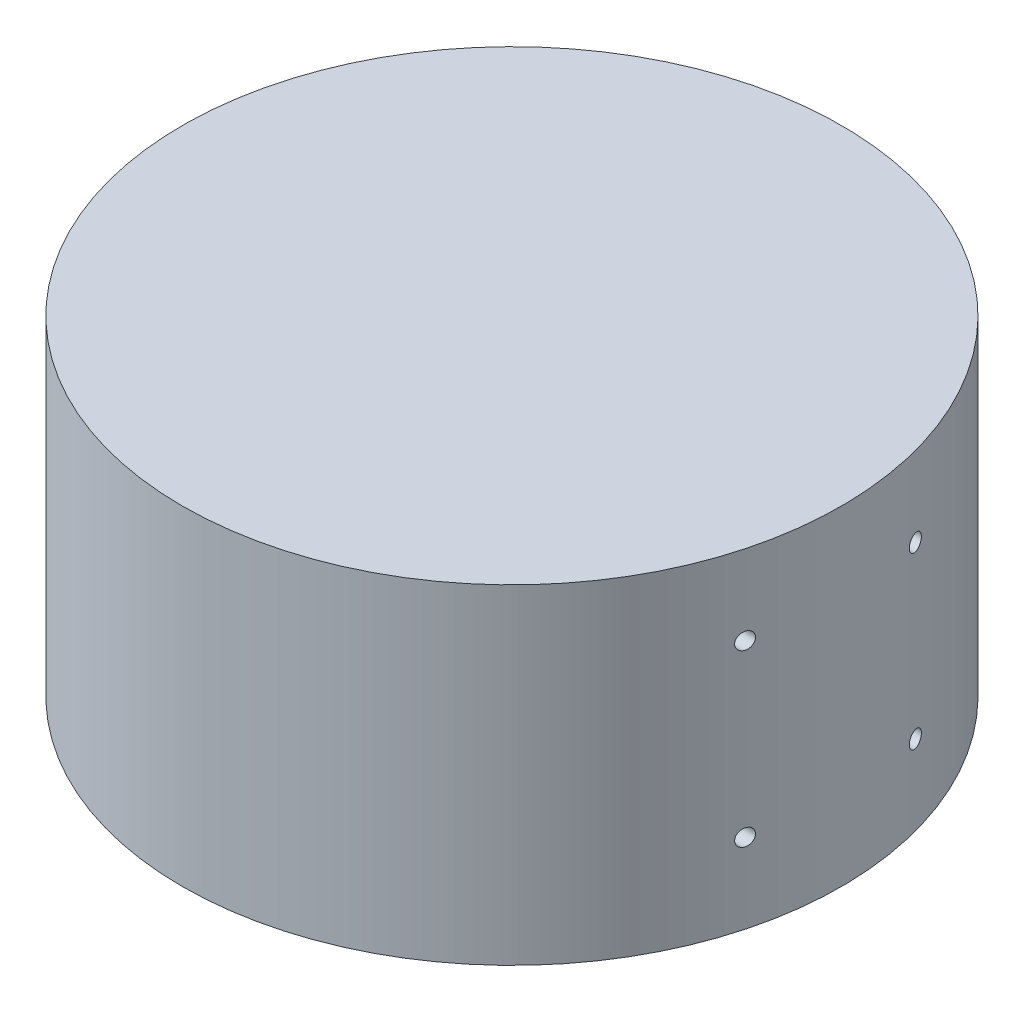
SolidWorks part; units mm, degrees
ref_plane "前视基准面" through (0, 0, 0) normal (0, 0, 1) x (1, 0, 0)
ref_plane "上视基准面" through (0, 0, 0) normal (0, 1, 0) x (1, 0, 0)
ref_plane "右视基准面" through (0, 0, 0) normal (1, 0, 0) x (0, 0, -1)
other "Configuration Table"
sketch "Sketch1" plane through (0, 0, 0) normal (0, 1, 0) x (1, 0, 0)
  circle A0 centre (0, 0) radius 60
extrude "Boss-Extrude1" add sketch "Sketch1" along normal blind 60
sketch "Sketch2" plane through (0, 0, 0) normal (0, 1, 0) x (1, 0, 0)
  circle A0 centre (0, 0) radius 10
extrude "Cut-Extrude1" cut sketch "Sketch2" along normal blind 20
sketch "Sketch3" plane through (0, 0, 0) normal (1, 0, 0) x (0, 0, -1)
  circle A0 centre (-15.5, 45.5) radius 1.5
  circle A1 centre (-15.5, 14.5) radius 1.5
  circle A2 centre (15.5, 14.5) radius 1.5
  circle A3 centre (15.5, 45.5) radius 1.5
extrude "Cut-Extrude2" cut sketch "Sketch3" along normal blind 100
sketch3d "3DSketch1"
  line L0 (0, 0, 0) -> (0, 100, 0) construction
ref_axis "Axis_J1" through (0, 0, 0) along (0, 1, 0)
ref_plane "Mate_Top" through (0, 60, 0) normal (0, 1, 0) x (1, 0, 0)
